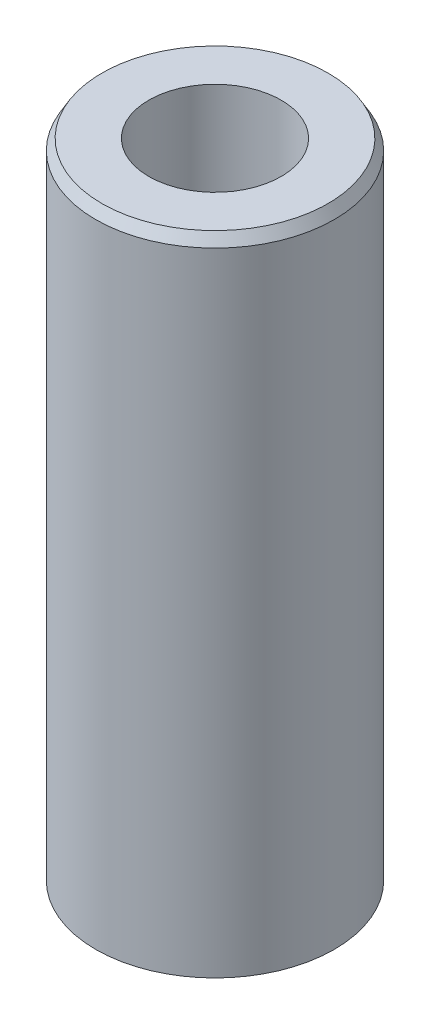
SolidWorks part; units mm, degrees
ref_plane "Front Plane" through (0, 0, 0) normal (0, 0, 1) x (1, 0, 0)
ref_plane "Top Plane" through (0, 0, 0) normal (0, 1, 0) x (1, 0, 0)
ref_plane "Right Plane" through (0, 0, 0) normal (1, 0, 0) x (0, 0, -1)
sketch "Sketch1" plane through (0, 0, 0) normal (0, 1, 0) x (1, 0, 0)
  circle A0 centre (0, 0) radius 27.5
  dimension "SHAFT_OD" = 55
extrude "Boss-Extrude1" add sketch "Sketch1" along normal blind 149.6216
sketch "Sketch2" plane through (0, 0, 0) normal (0, 1, 0) x (1, 0, 0)
  circle A0 centre (0, 0) radius 15.2598
  dimension "BORE_D" = 30.5195
extrude "Cut-Extrude1" cut sketch "Sketch2" along normal through all
chamfer "Chamfer1" distance 2.4808 angle 30 2 edges at (0, 149.6216, 27.5) (0, 0, 27.5) first distance on face at (0, 149.6216, 27.5) first distance on face at (0, 0, 15.2598)
